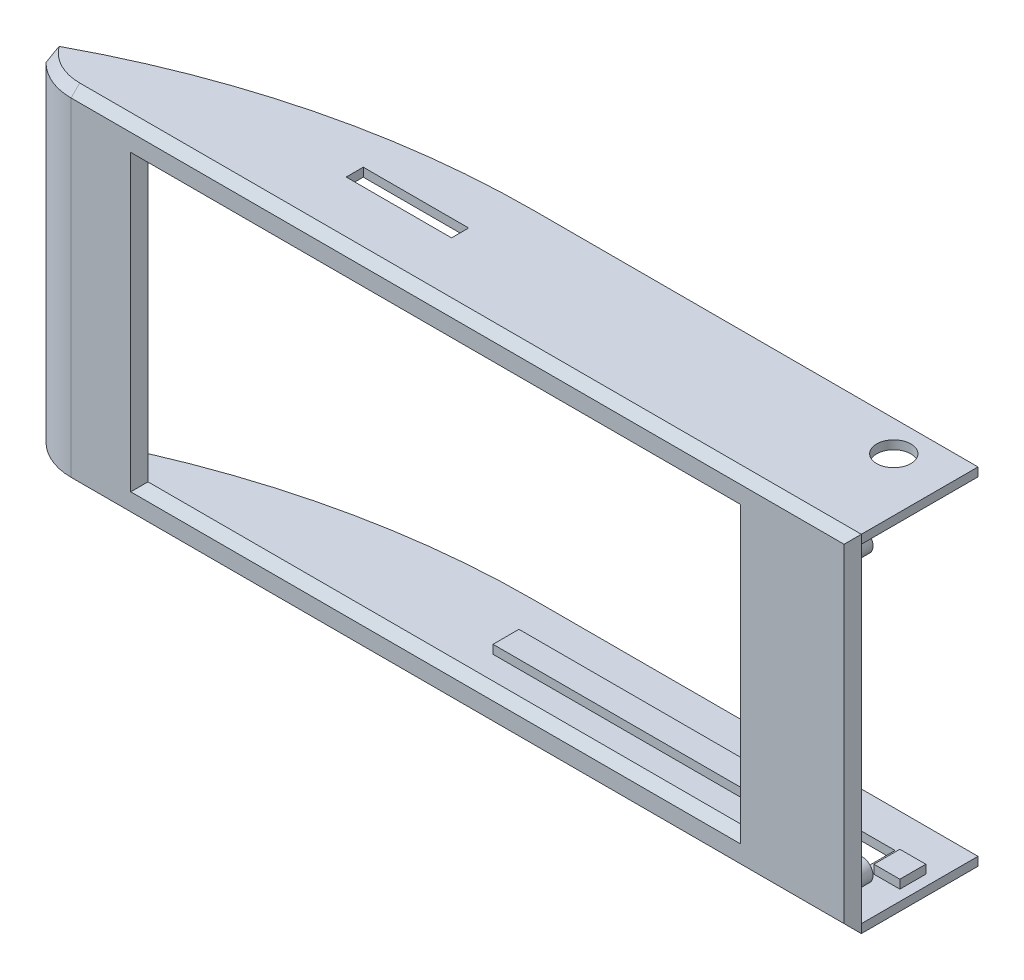
SolidWorks part; units mm, degrees
ref_plane "Front Plane" through (0, 0, 0) normal (0, 0, 1) x (1, 0, 0)
ref_plane "Top Plane" through (0, 0, 0) normal (0, 1, 0) x (1, 0, 0)
ref_plane "Right Plane" through (0, 0, 0) normal (1, 0, 0) x (0, 0, -1)
sketch "Sketch1" plane through (101441.594, 0, 0) normal (0, 0, 1) x (-1, 0, 0)
  line L1 (101382.549, 35) -> (101451.049, 35)
  line L2 (101382.549, 35) -> (101382.549, 3)
  line L3 (101382.549, 3) -> (101451.049, 3)
  line L8 (101458.949, 39) -> (101368.549, 39)
  line L9 (101458.949, -1) -> (101458.949, 39)
  line L10 (101368.549, -1) -> (101458.949, -1)
  line L11 (101368.549, 39) -> (101368.549, -1)
  line L12 (101451.049, 35) -> (101451.049, 3)
  point P8 (0, 0)
  point P9 (0, 0)
  point P10 (0, 0)
  point P15 (101370.1205, 49.9432)
  point P16 (101369.449, -21.0305)
  dimension "D2" = 68.5
  dimension "D3" = 14
  dimension "D4" = 4
  dimension "D5" = 4
  dimension "D6" = 90.4
  dimension "D1" = 40
extrude "Boss-Extrude1" add sketch "Sketch1" along normal blind 1
sketch "Sketch2" plane through (0, 0, 0) normal (0, 0, -1) x (-1, 0, 0)
  line L0 (-73.0451, 1) -> (17.3549, 1) construction
  line L1 (17.3549, -39) -> (-73.0451, -39) construction
  line L2 (-73.0451, -39) -> (-73.0451, 1) construction
  circle A0 centre (-70.1451, -2.5) radius 1.25
  circle A1 centre (-70.1451, -35.5) radius 1.25
  circle A2 centre (14.3549, -2.5) radius 1.25
  circle A3 centre (14.3549, -35.5) radius 1.25
  dimension "D4" = 2.5
  dimension "D1" = 3.5
  dimension "D2" = 3.5
  dimension "D3" = 2.9
  dimension "D5" = 2
extrude "Boss-Extrude2" add sketch "Sketch2" along normal blind 3
sketch "Sketch3" plane through (0, 1, 0) normal (0, 1, 0) x (1, 0, 0)
  line L0 (73.0451, 0) -> (-17.3549, 0) construction
  line L1 (-17.3549, -1) -> (-17.3549, 0) construction
  line L2 (-22.3549, 2.6834) -> (-22.3549, 1.101)
  line L3 (-17.3549, -1) -> (-17.3549, 0)
  arc A0 (-17.3549, 0) -> (-22.3549, 2.6834) centre (-17.3549, 6) cw
  arc A1 (-17.3549, -1) -> (-22.3549, 1.101) centre (-17.3549, 6) cw
  arc A3 (-17.3549, -1) -> (-23.1883, 2.1306) centre (-17.3549, 6) cw construction
  point P9 (-9.0835, 0.6617)
  dimension "D1" = 6
  dimension "D2" = 5
extrude "Boss-Extrude3" add sketch "Sketch3" against normal through all separate body
chamfer "Chamfer1" distance 1 angle 45 2 edges at (-20.0667, 1, 0.4534) (-20.0667, -39, 0.4534)
chamfer "Chamfer2" distance 1 angle 45 7 edges at (24.7951, -3, 1) (-9.4549, -19, 1) (24.7951, -35, 1) (59.0451, -19, 1) (27.8451, -39, 1) (73.0451, -19, 1) (27.8451, 1, 1)
ref_plane "Plane1" through (0, -39, 0) normal (0, 1, 0) x (1, 0, 0)
ref_plane "Plane2" through (0, 1, 0) normal (0, 1, 0) x (1, 0, 0)
sketch "Sketch6" plane through (0, 1, 0) normal (0, 1, 0) x (1, 0, 0)
  line L0 (73.0451, 0) -> (-17.3549, 0) construction
  line L1 (71.8188, 0) -> (61.8388, 0)
  line L2 (71.8188, 0) -> (71.8188, 13.9185)
  line L3 (71.8188, 13.9185) -> (61.8388, 13.9185)
  line L4 (61.8388, 0) -> (61.8388, 13.9185)
  line L5 (29.764, 0) -> (-0.962, 0)
  line L6 (29.764, 0) -> (29.764, 11.5588)
  line L7 (29.764, 11.5588) -> (-0.962, 11.5588)
  line L8 (-0.962, 0) -> (-0.962, 11.5588)
  line L10 (19.6612, 5.9892) -> (7.4739, 5.9892)
  line L11 (19.6612, 5.9892) -> (19.6612, 7.9655)
  line L12 (19.6612, 7.9655) -> (7.4739, 7.9655)
  line L13 (7.4739, 5.9892) -> (7.4739, 7.9655)
  circle A0 centre (66.8561, 9.9375) radius 1.9758
extrude "Boss-Extrude4" add sketch "Sketch6" against normal blind 1
sketch "Sketch8" plane through (0, 0, 0) normal (0, -1, 0) x (1, 0, 0)
  line L0 (29.764, 0) -> (29.764, -11.5588) construction
  line L1 (29.764, -8.6788) -> (24.764, -8.6788)
  line L2 (29.764, -8.6788) -> (29.764, -5.6788)
  line L3 (29.764, -5.6788) -> (24.764, -5.6788)
  line L4 (24.764, -8.6788) -> (24.764, -5.6788)
  line L5 (29.764, -11.5588) -> (-0.962, -11.5588) construction
  dimension "D1" = 5.88
  dimension "D2" = 3
  dimension "D3" = 5
extrude "Boss-Extrude6" add sketch "Sketch8" along normal blind 1
sketch "Sketch9" plane through (0, -39, 0) normal (0, 1, 0) x (1, 0, 0)
  line L1 (67.2061, 8.8062) -> (63.1589, 8.8062)
  line L2 (67.2061, 8.8062) -> (67.2061, 6.8122)
  line L3 (67.2061, 6.8122) -> (63.1589, 6.8122)
  line L4 (29.764, 0) -> (29.764, 11.5588)
  line L5 (29.764, 11.5588) -> (-0.962, 11.5588)
  line L6 (-0.962, 11.5588) -> (-0.962, 0)
  line L7 (-0.962, 0) -> (29.764, 0)
  line L8 (29.764, 0) -> (29.764, 11.5588)
  line L9 (29.764, 11.5588) -> (-0.962, 11.5588)
  line L10 (-0.962, 11.5588) -> (-0.962, 0)
  line L11 (-0.962, 0) -> (29.764, 0)
  line L12 (71.8188, 0) -> (71.8188, 13.9185)
  line L13 (61.8388, 0) -> (71.8188, 0)
  line L14 (61.8388, 13.9185) -> (61.8388, 0)
  line L15 (71.8188, 13.9185) -> (61.8388, 13.9185)
  line L16 (71.8188, 0) -> (71.8188, 13.9185)
  line L17 (61.8388, 0) -> (71.8188, 0)
  line L18 (61.8388, 13.9185) -> (61.8388, 0)
  line L19 (71.8188, 13.9185) -> (61.8388, 13.9185)
  line L20 (63.1589, 8.8062) -> (63.1589, 6.8122)
  dimension "D1" = 0
  dimension "D2" = 0
extrude "Boss-Extrude7" add sketch "Sketch9" along normal blind 1
sketch "Sketch10" plane through (0, -38, 0) normal (0, 1, 0) x (1, 0, 0)
  line L0 (71.8188, 0) -> (71.8188, 13.9185) construction
  line L1 (71.8188, 5.6785) -> (68.8188, 5.6785)
  line L2 (71.8188, 5.6785) -> (71.8188, 8.6785)
  line L3 (71.8188, 8.6785) -> (68.8188, 8.6785)
  line L4 (29.764, 5.6788) -> (29.764, 8.6788)
  line L5 (24.764, 5.6788) -> (29.764, 5.6788)
  line L6 (24.764, 8.6788) -> (24.764, 5.6788)
  line L7 (29.764, 8.6788) -> (24.764, 8.6788)
  line L8 (29.764, 5.6788) -> (29.764, 8.6788)
  line L9 (24.764, 5.6788) -> (29.764, 5.6788)
  line L10 (24.764, 8.6788) -> (24.764, 5.6788)
  line L11 (29.764, 8.6788) -> (24.764, 8.6788)
  line L12 (68.8188, 5.6785) -> (68.8188, 8.6785)
  line L13 (71.8188, 13.9185) -> (61.8388, 13.9185) construction
  point P12 (27.264, 8.6788)
  dimension "D2" = 8.24
  dimension "D3" = 3
  dimension "D4" = 3
  dimension "D1" = 0
extrude "Boss-Extrude8" add sketch "Sketch10" along normal blind 1
sketch "Sketch11" plane through (29.764, 0, 0) normal (1, 0, 0) x (0, 0, -1)
  line L8 (11.5588, 1) -> (0, 1)
  line L9 (0, 1) -> (0, 0)
  line L10 (0, 0) -> (5.6788, 0)
  line L11 (5.6788, 0) -> (5.6788, -1)
  line L12 (5.6788, -1) -> (8.6788, -1)
  line L13 (8.6788, -1) -> (8.6788, 0)
  line L14 (8.6788, 0) -> (11.5588, 0)
  line L15 (11.5588, 0) -> (11.5588, 1)
  line L16 (11.5588, 1) -> (0, 1)
  line L17 (0, 1) -> (0, 0)
  line L18 (0, 0) -> (5.6788, 0)
  line L19 (5.6788, 0) -> (5.6788, -1)
  line L20 (5.6788, -1) -> (8.6788, -1)
  line L21 (8.6788, -1) -> (8.6788, 0)
  line L22 (8.6788, 0) -> (11.5588, 0)
  line L23 (11.5588, 0) -> (11.5588, 1)
  dimension "D1" = 0
extrude "Boss-Extrude9" add sketch "Sketch11" along normal up to vertex (32.0748 mm away) up to point (61.8388, 1, 0)
sketch "Sketch12" plane through (29.764, 0, 0) normal (1, 0, 0) x (0, 0, -1)
  line L8 (0, -39) -> (11.5588, -39)
  line L9 (11.5588, -39) -> (11.5588, -38)
  line L10 (11.5588, -38) -> (8.6788, -38)
  line L11 (8.6788, -38) -> (8.6788, -37)
  line L12 (8.6788, -37) -> (5.6788, -37)
  line L13 (5.6788, -37) -> (5.6788, -38)
  line L14 (5.6788, -38) -> (0, -38)
  line L15 (0, -38) -> (0, -39)
  line L16 (0, -39) -> (11.5588, -39)
  line L17 (11.5588, -39) -> (11.5588, -38)
  line L18 (11.5588, -38) -> (8.6788, -38)
  line L19 (8.6788, -38) -> (8.6788, -37)
  line L20 (8.6788, -37) -> (5.6788, -37)
  line L21 (5.6788, -37) -> (5.6788, -38)
  line L22 (5.6788, -38) -> (0, -38)
  line L23 (0, -38) -> (0, -39)
  dimension "D1" = 0
extrude "Boss-Extrude10" add sketch "Sketch12" along normal up to vertex (32.0748 mm away) up to point (61.8388, -39, -13.9185)
sketch "Sketch13" plane through (0, -39, 0) normal (0, -1, 0) x (1, 0, 0)
  line L1 (-22.3549, -5.5334) -> (-22.3549, -2.6834) construction
  line L2 (-17.3549, 0) -> (-0.962, 0) construction
  line L3 (-17.3549, 0) -> (-0.962, 0)
  line L4 (-0.962, -11.5588) -> (-0.962, 0) construction
  line L5 (-0.962, -11.5588) -> (-0.962, 0)
  arc A0 (-22.3549, -5.5334) -> (-0.962, -11.5588) centre (15.2842, 87.1127) ccw
  arc A2 (-17.3549, 0) -> (-22.3549, -2.6834) centre (-17.3549, -6) ccw construction
  arc A3 (-17.3549, 0) -> (-22.3549, -2.6834) centre (-17.3549, -6) ccw
  arc A4 (-22.3549, -2.6834) -> (-23.2939, -5.1463) centre (-17.3549, -6) ccw
  arc A5 (-22.3549, -5.5334) -> (-23.2939, -5.1463) centre (15.2842, 87.1127) cw
  dimension "D1" = 100
  dimension "D2" = 2.85
extrude "Boss-Extrude11" add sketch "Sketch13" against normal up to surface (1 mm away) up to face at (54.6666, -38, -7.9669)
sketch "Sketch14" plane through (0, 1, 0) normal (0, 1, 0) x (1, 0, 0)
  line L0 (-0.962, 0) -> (-17.3549, 0)
  line L1 (-0.962, 11.5588) -> (-0.962, 0)
  arc A0 (-22.3549, 2.6834) -> (-17.3549, 0) centre (-17.3549, 6) ccw construction
  arc A1 (-23.2939, 5.1463) -> (-22.3549, 2.6834) centre (-17.3549, 6) ccw construction
  arc A2 (-0.962, 11.5588) -> (-23.2939, 5.1463) centre (15.2842, -87.1127) ccw construction
  arc A3 (-22.3549, 2.6834) -> (-17.3549, 0) centre (-17.3549, 6) ccw
  arc A4 (-23.2939, 5.1463) -> (-22.3549, 2.6834) centre (-17.3549, 6) ccw
  arc A5 (-0.962, 11.5588) -> (-23.2939, 5.1463) centre (15.2842, -87.1127) ccw
extrude "Boss-Extrude12" add sketch "Sketch14" against normal up to surface (1 mm away) up to face at (43.3014, 0, -7.1788)
sketch "Sketch15" plane through (0, 1, 0) normal (0, 1, 0) x (1, 0, 0)
  line L0 (61.8388, 13.9185) -> (61.8388, 11.5588) construction
  line L1 (61.8388, 13.9185) -> (61.8388, 11.5588)
  line L4 (61.8388, 13.9185) -> (-0.962, 11.5588)
  line L5 (-0.962, 11.5588) -> (61.8388, 11.5588)
extrude "Boss-Extrude13" add sketch "Sketch15" against normal up to surface (1 mm away) up to face at (43.3014, 0, -7.1788)
sketch "Sketch16" plane through (0, -39, 0) normal (0, -1, 0) x (1, 0, 0)
  line L0 (-0.962, -11.5588) -> (61.8388, -13.9185) construction
  line L1 (-0.962, -11.5588) -> (61.8388, -13.9185)
  line L2 (61.8388, -13.9185) -> (61.8388, -11.5588) construction
  line L3 (61.8388, -11.5588) -> (-0.962, -11.5588) construction
  line L4 (61.8388, -13.9185) -> (61.8388, -11.5588)
  line L5 (61.8388, -11.5588) -> (-0.962, -11.5588)
extrude "Boss-Extrude14" add sketch "Sketch16" against normal up to surface (1 mm away) up to face at (40.3303, -38, -7.289)
sketch "Sketch18" plane through (0, 1, 0) normal (0, 1, 0) x (1, 0, 0)
  line L4 (71.8188, 0) -> (71.8188, 13.9185)
  line L5 (71.8188, 13.9185) -> (61.8388, 13.9185)
  line L6 (61.8388, 13.9185) -> (-0.962, 11.5588)
  line L7 (-17.3549, 0) -> (71.8188, 0)
  line L8 (71.8188, 0) -> (71.8188, 13.9185)
  line L9 (71.8188, 13.9185) -> (61.8388, 13.9185)
  line L10 (61.8388, 13.9185) -> (-0.962, 11.5588)
  line L11 (-17.3549, 0) -> (71.8188, 0)
  arc A3 (-0.962, 11.5588) -> (-23.2939, 5.1463) centre (15.2842, -87.1127) ccw
  arc A4 (-23.2939, 5.1463) -> (-22.3549, 2.6834) centre (-17.3549, 6) ccw
  arc A5 (-22.3549, 2.6834) -> (-17.3549, 0) centre (-17.3549, 6) ccw
  arc A6 (-0.962, 11.5588) -> (-23.2939, 5.1463) centre (15.2842, -87.1127) ccw
  arc A7 (-23.2939, 5.1463) -> (-22.3549, 2.6834) centre (-17.3549, 6) ccw
  arc A8 (-22.3549, 2.6834) -> (-17.3549, 0) centre (-17.3549, 6) ccw
  dimension "D1" = 0
extrude "Cut-Extrude1" cut sketch "Sketch18" against normal blind 1
sketch "Sketch17" plane through (0, 1, 0) normal (0, 1, 0) x (1, 0, 0)
  line L0 (73.0451, 13.49) -> (73.0451, 0)
  line L2 (73.0477, 13.49) -> (21.6451, 13.49)
  line L4 (73.0451, 0) -> (-17.3549, 0)
  line L5 (71.8188, 0) -> (71.8188, 13.9185) construction
  line L11 (19.6612, 5.9892) -> (19.6612, 7.9655)
  line L12 (7.4739, 5.9892) -> (19.6612, 5.9892)
  line L13 (7.4739, 7.9655) -> (7.4739, 5.9892)
  line L14 (19.6612, 7.9655) -> (7.4739, 7.9655)
  arc A1 (21.6451, 13.49) -> (-22.211, 2.476) centre (21.6451, -79.331) ccw
  arc A3 (-22.211, 2.476) -> (-17.3549, 0) centre (-17.3549, 6) ccw
  circle A5 centre (66.8561, 9.9375) radius 1.9758
  point P3 (73.0104, 13.3702)
  point P10 (73.3869, 0)
  point P13 (-22.1511, 2.3949)
  dimension "D1" = 92.821
  dimension "D5" = 3.9517
  dimension "D6" = 6
  dimension "D2" = 1.2289
  dimension "D3" = 50.1737
  dimension "D4" = 94.0298
  dimension "D7" = 7.4739
  dimension "D8" = 19.6612
  dimension "D9" = 66.8561
  dimension "D10" = 17.3549
  dimension "D11" = 5.9892
  dimension "D12" = 7.9655
  dimension "D13" = 9.9375
extrude "Boss-Extrude15" add sketch "Sketch17" against normal blind 1 contours A1 A3 L4 L0 L2 A5 L14 L11 L12 L13 region at (30.6754, 1, -6.2222)
sketch "Sketch19" plane through (0, -39, 0) normal (0, -1, 0) x (1, 0, 0)
  line L4 (-0.962, -11.5588) -> (61.8388, -13.9185)
  line L5 (61.8388, -13.9185) -> (71.8188, -13.9185)
  line L6 (71.8188, -13.9185) -> (71.8188, 0)
  line L7 (71.8188, 0) -> (-17.3549, 0)
  line L8 (-0.962, -11.5588) -> (61.8388, -13.9185)
  line L9 (61.8388, -13.9185) -> (71.8188, -13.9185)
  line L10 (71.8188, -13.9185) -> (71.8188, 0)
  line L11 (71.8188, 0) -> (-17.3549, 0)
  arc A3 (-17.3549, 0) -> (-22.3549, -2.6834) centre (-17.3549, -6) ccw
  arc A4 (-22.3549, -2.6834) -> (-23.2939, -5.1463) centre (-17.3549, -6) ccw
  arc A5 (-23.2939, -5.1463) -> (-0.962, -11.5588) centre (15.2842, 87.1127) ccw
  arc A6 (-17.3549, 0) -> (-22.3549, -2.6834) centre (-17.3549, -6) ccw
  arc A7 (-22.3549, -2.6834) -> (-23.2939, -5.1463) centre (-17.3549, -6) ccw
  arc A8 (-23.2939, -5.1463) -> (-0.962, -11.5588) centre (15.2842, 87.1127) ccw
  dimension "D1" = 0
extrude "Cut-Extrude2" cut sketch "Sketch19" against normal blind 1
sketch "Sketch20" plane through (0, -38, 0) normal (0, -1, 0) x (1, 0, 0)
  line L3 (21.6451, -13.49) -> (73.0451, -13.49)
  line L4 (73.0451, -13.49) -> (73.0451, 0)
  line L5 (73.0451, 0) -> (-17.3549, 0)
  line L6 (21.6451, -13.49) -> (73.0451, -13.49)
  line L7 (73.0451, -13.49) -> (73.0451, 0)
  line L8 (73.0451, 0) -> (-17.3549, 0)
  line L14 (67.6677, -6.28) -> (62.6677, -6.28)
  line L15 (62.6677, -6.28) -> (62.6677, -9.28)
  line L16 (62.6677, -9.28) -> (67.6677, -9.28)
  line L17 (67.6677, -9.28) -> (67.6677, -6.28)
  arc A2 (-22.211, -2.476) -> (21.6451, -13.49) centre (21.6451, 79.331) ccw
  arc A3 (-17.3549, 0) -> (-22.211, -2.476) centre (-17.3549, -6) ccw
  arc A4 (-22.211, -2.476) -> (21.6451, -13.49) centre (21.6451, 79.331) ccw
  arc A5 (-17.3549, 0) -> (-22.211, -2.476) centre (-17.3549, -6) ccw
  dimension "D1" = 0
extrude "Boss-Extrude16" add sketch "Sketch20" along normal blind 1
sketch "Sketch21" plane through (0, -39, 0) normal (0, -1, 0) x (1, 0, 0)
  line L0 (-22.211, -2.476) -> (-22.3549, -1.101)
  line L1 (-22.3549, -1.101) -> (-22.3549, -2.6834)
  arc A0 (-22.211, -2.476) -> (-22.3549, -2.6834) centre (-17.3549, -6) ccw construction
  arc A1 (-22.211, -2.476) -> (-22.3549, -2.6834) centre (-17.3549, -6) ccw
extrude "Cut-Extrude3" cut sketch "Sketch21" against normal through all both and the other way through all
